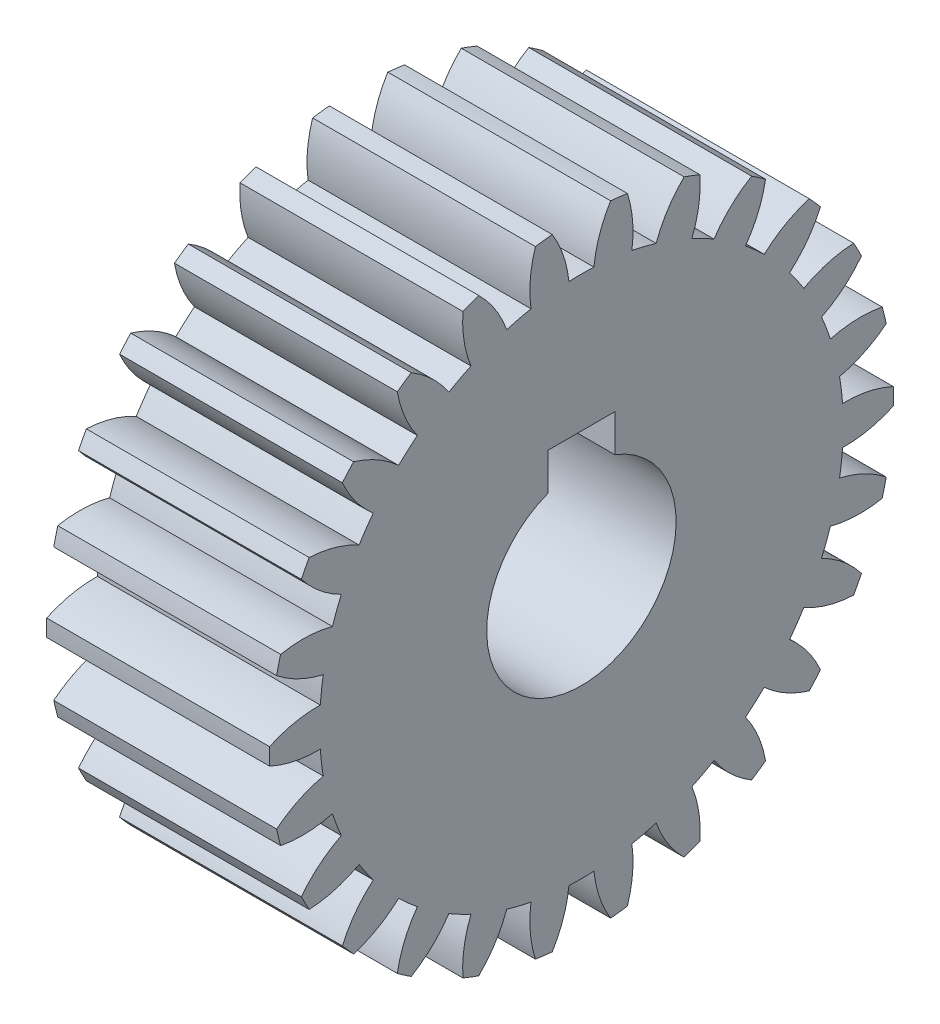
SolidWorks part; units mm, degrees
ref_plane "Plane1" through (0, 0, 0) normal (0, 0, 1) x (1, 0, 0)
ref_plane "Plane2" through (0, 0, 0) normal (0, 1, 0) x (1, 0, 0)
ref_plane "Plane3" through (0, 0, 0) normal (1, 0, 0) x (0, 0, -1)
sketch "HoldingSke" plane through (0, 0, 0) normal (0, 1, 0) x (1, 0, 0)
  line L0 (0, 0) -> (0.4494, -0.2192)
  line L1 (-15, 0) -> (100, 0) construction
  line L2 (0, 0) -> (-2.1039, 2.3779)
  line L3 (0, 0) -> (-11.863, 4.5341)
  line L4 (0, 0) -> (7.762, 3.7858)
  line L5 (0, 0) -> (-46.8476, -17.4728)
  line L6 (0, 0) -> (-16.5793, -11.1861)
  line L7 (-2.1039, 2.3779) -> (8.6586, 51.2059)
  line L8 (-76.2, 54.61) -> (-73.4, 54.61)
  line L9 (-67.7845, 28.3722) -> (-49.3413, 33.142)
  line L10 (-76.2, 71.12) -> (104.1128, 71.12)
  line L11 (0, 0) -> (-20, 0)
  line L12 (-76.2, 101.6) -> (-76.133, 101.6)
  line L13 (24.9733, 27.94) -> (52.9518, 28.4284)
  line L14 (24.9733, 27.94) -> (24.9743, 27.94)
  line L15 (24.9733, 27.94) -> (100.4006, 29.5858)
  line L16 (-63.627, -2) -> (-12.827, -2)
  circle A0 centre (0, 0) radius 8.5
  circle A1 centre (0, 0) radius 23.499
  circle A2 centre (0, 0) radius 37.5
  circle A3 centre (0, 0) radius 8.5
  dimension "Num_teeth" = 26
  dimension "Pitch_radius" = 180.3128
  dimension "Width" = 20
  dimension "Thickness" = 20
sketch "BasProSke" plane through (0, 0, 0) normal (0, 1, 0) x (1, 0, 0)
  line L0 (-10, 0) -> (60, 0) construction
  line L1 (0, 0) -> (0, 28)
  line L2 (0, 0) -> (20, 0)
  line L3 (20, 0) -> (20, 28)
  line L4 (20, 28) -> (0, 28)
  dimension "Thickness" = 20
  dimension "Diameter" = 56
revolve "Base-Revolve" add sketch "BasProSke" angle 360 about L0
sketch "TooCutSke" plane through (0, 0, 0) normal (1, 0, 0) x (0, 0, -1)
  line L1 (0, 0) -> (0, 107) construction
  line L2 (0, 0) -> (-1.6871, 25.9452) construction
  line L3 (0, 0) -> (-6.2581, 51.5402) construction
  line L4 (-1.6871, 25.9452) -> (-3.1291, 25.7701) construction
  arc A0 (1.1217, 23.4722) -> (-1.1217, 23.4722) centre (0, 0) ccw
  arc A1 (2.6361, 27.9012) -> (-2.6361, 27.9012) centre (0, 0) ccw
  circle A2 centre (0, 0) radius 26 construction
  circle A3 centre (0, 0) radius 25.1718 construction
  arc A4 (-1.1217, 23.4722) -> (-2.6361, 27.9012) centre (-11.4671, 22.4082) ccw
  arc A5 (2.6361, 27.9012) -> (1.1217, 23.4722) centre (11.4671, 22.4082) ccw
extrude "ToothCut" cut sketch "TooCutSke" along normal through all
fillet "Breaks" [suppressed] radius 0.04 tangent propagation no
fillet "RootFillets" [suppressed] radius 0.501
pattern_circular "TeethCuts" count 26 every 13.846 about axis through (-10, 0, 0) along (1, 0, 0) of "ToothCut", "RootFillets", "Breaks"
sketch "HubNeaOneSke" plane through (0, 0, 0) normal (-1, 0, 0) x (0, 0, 1)
  circle A0 centre (0, 0) radius 23.499
  dimension "Diameter" = 46.998
extrude "HubNearOne" [suppressed] add sketch "HubNeaOneSke" along normal blind 30.0001
sketch "HubNeaBotSke" plane through (0, 0, 0) normal (-1, 0, 0) x (0, 0, 1)
  circle A0 centre (0, 0) radius 23.499
  dimension "Diameter" = 46.998
extrude "HubNearBoth" [suppressed] add sketch "HubNeaBotSke" along normal blind 15
ref_plane "FarPln" through (20, 0, 0) normal (1, 0, 0) x (0, 0, -1)
sketch "HubFarSke" plane through (20, 0, 0) normal (1, 0, 0) x (0, 0, -1)
  circle A0 centre (0, 0) radius 23.499
  dimension "Diameter" = 46.998
extrude "HubFar" [suppressed] add sketch "HubFarSke" along normal blind 15
sketch "BorSke" plane through (0, 0, 0) normal (1, 0, 0) x (0, 0, -1)
  circle A0 centre (0, 0) radius 8.5
  dimension "Diameter" = 17
extrude "Bore" cut sketch "BorSke" along normal mid plane 100.0001
sketch "KeySke" plane through (0, 0, 0) normal (1, 0, 0) x (0, 0, -1)
  line L0 (-3, 0) -> (-3, 11.3)
  line L1 (-3, 11.3) -> (3, 11.3)
  line L2 (3, 11.3) -> (3, 0)
  line L3 (0, 0) -> (0, 34) construction
  line L4 (-3, 0) -> (3, 0)
  dimension "Width" = 6
extrude "Keyway" cut sketch "KeySke" along normal mid plane 100.0001
pattern_circular "Keyway2" [suppressed] count 2 every 90 about axis through (-10, 0, 0) along (1, 0, 0) reverse direction yes
equation "' \"Module@HoldingSke\" = 6.35"
equation "' \"Num_teeth@HoldingSke\" = 12"
equation "' \"Ap@HoldingSke\" =  20"
equation "' \"Ap@HoldingSke\" = 20"
equation "' \"Width@HoldingSke\" = 0.5 * 25.4"
equation "' \"Hub_dia@HoldingSke\"= 1 * 25.4"
equation "' \"Hub_dia@HoldingSke\" = 1 * 25.4"
equation "' \"Overall_len@HoldingSke\" = 1.0 * 25.4"
equation "' \"Bore@HoldingSke\" = 0.75 * 25.4"
equation "' \"T_dim@HoldingSke\" = 0.1 * 25.4"
equation "' \"Width@KeySke\" = 0.25 * 25.4"
equation "' \"Show_teeth@HoldingSke\" = 13"
equation "' \"Backlash@HoldingSke\" = 0.009 * 25.4"
equation "' \"Addendum_fac@HoldingSke\" = 1.0"
equation "' \"Dedendum_fac@HoldingSke\" = 1.25"
equation "' \"Dedendum_add@HoldingSke\" = 0.00005 * 25.4"
equation "' \"Clearance_fac@HoldingSke\" = 0.25"
equation "\"Pitch@HoldingSke\" = 1 / \"Module@HoldingSke\""
equation "\"Overcut_dia@TooCutSke\" = (\"Num_teeth@HoldingSke\" + 2 * \"Addendum_fac@HoldingSke\") / \"Pitch@HoldingSke\" + 0.002 * 25.4"
equation "\"Pitch_dia@TooCutSke\" = \"Num_teeth@HoldingSke\" / \"Pitch@HoldingSke\""
equation "\"Base_dia@TooCutSke\" = \"Num_teeth@HoldingSke\" / \"Pitch@HoldingSke\" * cos((\"Ap@HoldingSke\"  * 3.14159265 / 180))"
equation "\"Root_dia@TooCutSke\" = (\"Num_teeth@HoldingSke\" + 2) / \"Pitch@HoldingSke\" - 2 * (\"Addendum_fac@HoldingSke\" + \"Dedendum_fac@HoldingSke\") / \"Pitch@HoldingSke\" - \"Dedendum_add@HoldingSke\" * 2"
equation "\"Half_ang@TooCutSke\" = 180 / \"Num_teeth@HoldingSke\""
equation "\"Half_CT@TooCutSke\" = \"Num_teeth@HoldingSke\" / \"Pitch@HoldingSke\" * sin((3.14159265 / 2 / \"Num_teeth@HoldingSke\")) / 2 - 7 * \"Backlash@HoldingSke\" / 4"
equation "\"Flank_rad@TooCutSke\" = \"Num_teeth@HoldingSke\" / \"Pitch@HoldingSke\" / 5"
equation "\"Radius@RootFillets\" = \"Clearance_fac@HoldingSke\" / \"Pitch@HoldingSke\" + \"Dedendum_add@HoldingSke\""
equation "\"Break_rad@Breaks\" = 0.02 / \"Pitch@HoldingSke\""
equation "\"Thickness@HoldingSke\" = \"Width@HoldingSke\""
equation "\"OAL@HoldingSke\" = \"Thickness@HoldingSke\""
equation "\"MHD@HoldingSke\" = (\"Num_teeth@HoldingSke\" + 2) / \"Pitch@HoldingSke\" - 2 * (\"Addendum_fac@HoldingSke\" + \"Dedendum_fac@HoldingSke\")  / \"Pitch@HoldingSke\" - \"Dedendum_add@HoldingSke\" * 2"
equation "\"MBD@HoldingSke\" = (\"Num_teeth@HoldingSke\" + 2) / \"Pitch@HoldingSke\" - 2 * (\"Addendum_fac@HoldingSke\" + \"Dedendum_fac@HoldingSke\")  / \"Pitch@HoldingSke\" - \"Dedendum_add@HoldingSke\" * 2 - 0.002 * 25.4"
equation "\"MHD@HoldingSke\" = ((sgn( \"MHD@HoldingSke\" - \"Hub_dia@HoldingSke\" )-1)*( \"MHD@HoldingSke\" - \"Hub_dia@HoldingSke\" ))/-2+ \"Hub_dia@HoldingSke\""
equation "\"MBD@HoldingSke\" = ((sgn( \"MBD@HoldingSke\" - \"Bore@HoldingSke\" )-1)*( \"MBD@HoldingSke\" - \"Bore@HoldingSke\" ))/-2+ \"Bore@HoldingSke\""
equation "\"OAL@HoldingSke\" = ((sgn( \"OAL@HoldingSke\" - \"Overall_len@HoldingSke\" )+1)*( \"OAL@HoldingSke\" - \"Overall_len@HoldingSke\" ))/2 + \"Overall_len@HoldingSke\" + 0.000002 * 25.4"
equation "\"Num_teeth@TeethCuts\" = int( \"Show_teeth@HoldingSke\" ) + 1"
equation "\"Num_teeth@TeethCuts\" = ((sgn( \"Num_teeth@TeethCuts\" - \"Num_teeth@HoldingSke\" )-1)*( \"Num_teeth@TeethCuts\" - \"Num_teeth@HoldingSke\" ))/-2+ \"Num_teeth@HoldingSke\""
equation "\"Num_teeth@TeethCuts\" = ((sgn( \"Num_teeth@TeethCuts\" - 2.0)+1)*( \"Num_teeth@TeethCuts\" - 2.0))/2 +2.0"
equation "\"Angle@TeethCuts\" = 360.0 / \"Num_teeth@HoldingSke\""
equation "\"Diameter@BasProSke\" = (\"Num_teeth@HoldingSke\" + 2 * \"Addendum_fac@HoldingSke\") / \"Pitch@HoldingSke\""
equation "\"Thickness@BasProSke\"  = \"Thickness@HoldingSke\""
equation "' \"Fillet_rad@BasProSke\" =  \"Thickness@HoldingSke\" * 0.05"
equation "' \"Fillet_rad@BasProSke\" = \"Thickness@HoldingSke\" * 0.05"
equation "\"MHD@HoldingSke\" = ((sgn( \"MHD@HoldingSke\" - \"Root_dia@TooCutSke\" )-1)*( \"MHD@HoldingSke\" - \"Root_dia@TooCutSke\" ))/-2+ \"Root_dia@TooCutSke\""
equation "\"Diameter@HubNeaOneSke\" = \"MHD@HoldingSke\""
equation "\"Length@HubNearOne\" = \"OAL@HoldingSke\" - \"Thickness@BasProSke\""
equation "\"Diameter@HubNeaBotSke\" = \"MHD@HoldingSke\""
equation "\"Length@HubNearBoth\" = ( \"OAL@HoldingSke\" - \"Thickness@BasProSke\" ) / 2.0"
equation "\"Thickness@FarPln\" = \"Thickness@BasProSke\""
equation "\"Diameter@HubFarSke\" = \"MHD@HoldingSke\""
equation "\"Length@HubFar\" = ( \"OAL@HoldingSke\" - \"Thickness@BasProSke\" ) / 2.0"
equation "\"Diameter@BorSke\" = \"MBD@HoldingSke\""
equation "\"D1@Bore\" = \"OAL@HoldingSke\" * 2.0"
equation "\"D1@Keyway\" = \"OAL@HoldingSke\" * 2.0"
equation "\"Offset@KeySke\" = \"T_dim@HoldingSke\" + \"MBD@HoldingSke\" / 2.0"
